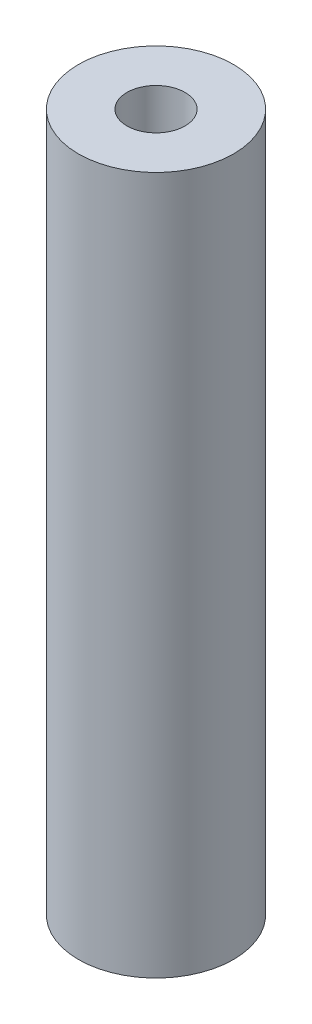
SolidWorks part; units mm, degrees
ref_plane "前视基准面" through (0, 0, 0) normal (0, 0, 1) x (1, 0, 0)
ref_plane "上视基准面" through (0, 0, 0) normal (0, 1, 0) x (1, 0, 0)
ref_plane "右视基准面" through (0, 0, 0) normal (1, 0, 0) x (0, 0, -1)
other "Configuration Table"
sketch "草图1" plane through (0, 0, 0) normal (0, 1, 0) x (1, 0, 0)
  circle A0 centre (0, 0) radius 2
  circle A1 centre (0, 0) radius 0.75
  dimension "D1" = 1.5
  dimension "D2" = 4
extrude "凸台-拉伸1" add sketch "草图1" along normal blind 18 contours A0 | A1
